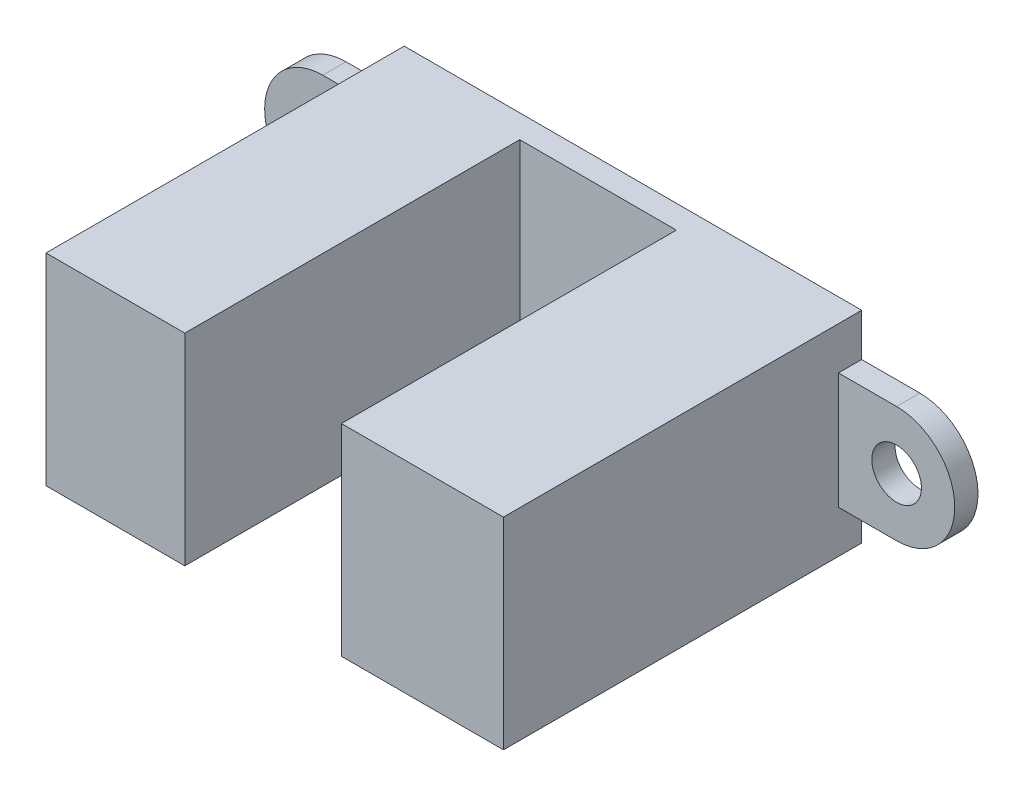
SolidWorks part; units mm, degrees
ref_plane "Front Plane" through (0, 0, 0) normal (0, 0, 1) x (1, 0, 0)
ref_plane "Top Plane" through (0, 0, 0) normal (0, 1, 0) x (1, 0, 0)
ref_plane "Right Plane" through (0, 0, 0) normal (1, 0, 0) x (0, 0, -1)
sketch "Sketch1" plane through (0, 0, 0) normal (0, 0, 1) x (1, 0, 0)
  line L0 (0, 6.5) -> (0, -6.5) construction
  line L1 (-14.75, -6.5) -> (14.75, -6.5)
  line L2 (-14.75, -6.5) -> (-14.75, 6.5)
  line L3 (-14.75, 6.5) -> (14.75, 6.5)
  line L4 (14.75, -6.5) -> (14.75, 6.5)
  line L5 (-14.75, -6.5) -> (14.75, 6.5) construction
  line L6 (-14.75, 6.5) -> (14.75, -6.5) construction
  line L7 (14.75, 3.75) -> (18.5, 3.75)
  line L8 (14.75, 3.75) -> (14.75, -3.75)
  line L9 (14.75, -3.75) -> (18.5, -3.75)
  line L10 (18.5, 3.75) -> (18.5, -3.75)
  line L11 (-14.75, -3.75) -> (-18.5, -3.75)
  line L12 (-18.5, 3.75) -> (-18.5, -3.75)
  line L13 (-14.75, 3.75) -> (-18.5, 3.75)
  line L14 (-14.75, 3.75) -> (-14.75, -3.75)
  circle A0 centre (18.5, 0) radius 3.75
  circle A1 centre (-18.5, 0) radius 3.75
  point P0 (0, 0)
  dimension "D3" = 7.5
  dimension "D1" = 13
  dimension "D2" = 29.5
extrude "Back Plate" add sketch "Sketch1" along normal blind 1.5 contours A1 L12 | L13 A1 L14 | A1 L12 | L2 A1 L11 | L1 L4 L8 L3 L2 L14 | A0 L4 L9 | A0 L7 L8 | L10 A0 | L10 A0 region at (0, 0, 0) region at (-15.5876, -2.9124, 0) region at (15.5876, -2.9124, 0) region at (-15.5876, 2.9124, 0) region at (-16.9085, 0, 0) region at (-20.0915, 0, 0) region at (15.5876, 2.9124, 0) region at (16.9085, 0, 0) region at (20.0915, 0, 0)
sketch "Sketch2" plane through (0, 0, 0) normal (1, 0, 0) x (0, 0, -1)
  line L0 (-1.5, -6.5) -> (0, -6.5) construction
  line L1 (-1.5, 6.5) -> (-23.1, 6.5)
  line L2 (-1.5, 6.5) -> (-1.5, -6.5)
  line L3 (-1.5, -6.5) -> (-23.1, -6.5)
  line L4 (-23.1, 6.5) -> (-23.1, -6.5)
  dimension "D1" = 13
  dimension "D2" = 21.6
extrude "Detector Side" add sketch "Sketch2" against normal blind 10.45 from surface starting at face at (14.75, -5.125, 0.75)
extrude "Emitter Side" add sketch "Sketch2<2>" along normal blind 8.95 from surface starting at face at (-14.75, -5.125, 0.75)
sketch "Sketch2<2>" plane through (0, 0, 0) normal (1, 0, 0) x (0, 0, -1) same geometry as "Sketch2"
hole_wizard "Ø3.2 (3.2) Diameter Hole1" positions "Sketch3" profile "Sketch4" hole size "Ø3.2" standard "ANSI Metric"
sketch "Sketch3" plane through (0, 0, 0) normal (0, 0, -1) x (-1, 0, 0)
  line L0 (-18.5, 3.75) -> (-18.5, -3.75) construction
  line L2 (-22.25, 0) -> (22.25, 0) construction
  line L4 (18.5, 3.75) -> (18.5, -3.75) construction
  arc A0 (-18.5, 3.75) -> (-18.5, -3.75) centre (-18.5, 0) ccw construction
  arc A1 (18.5, -3.75) -> (18.5, 3.75) centre (18.5, 0) ccw construction
  point P0 (-18.5, 0)
  point P2 (18.5, 0)
  point P26 (0, 0)
  point P27 (0, 0)
  point P28 (0, 0)
sketch "Sketch4" plane through (18.5, 0, 0) normal (1, 0, 0) x (0, 1, 0)
  line L0 (0, 0) -> (0, 4.9614)
  line L1 (0, 4.9614) -> (1.6, 4)
  line L2 (1.6, 4) -> (1.6, 0)
  line L5 (1.6, 0) -> (0, 0)
  line L10 (0, 4.9614) -> (-1.6, 4) construction
  line L11 (0, -6.35) -> (0, 107.95) construction
  dimension "Hole Dia." = 3.2
  dimension "Hole Depth" = 4
  dimension "Drill Angle" = 118
